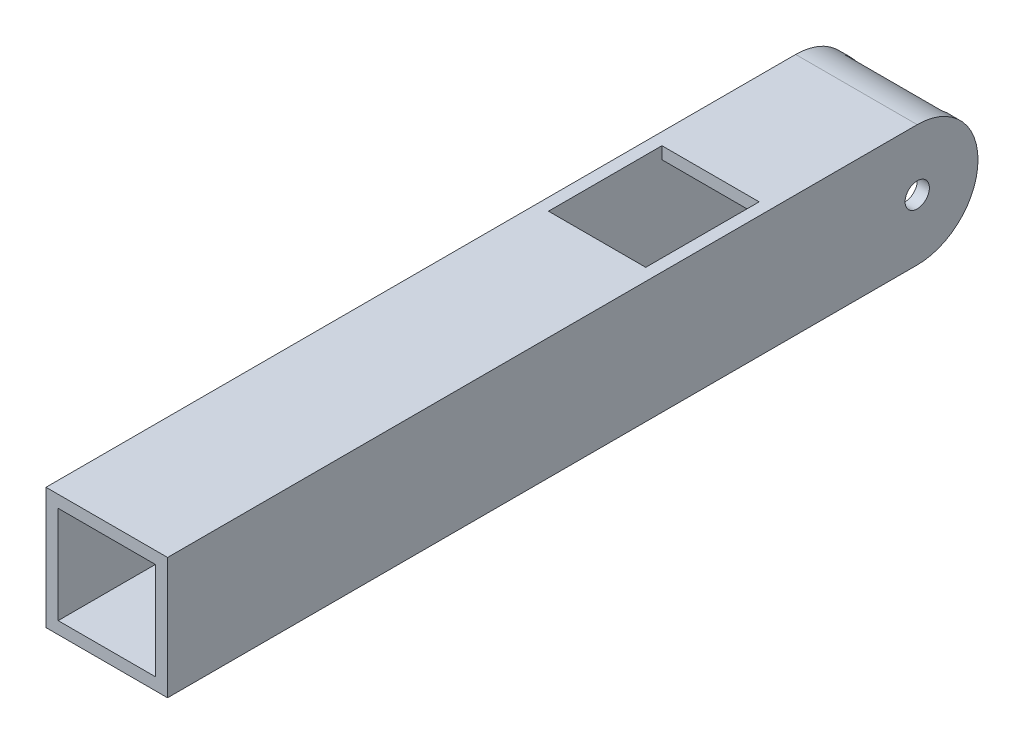
SolidWorks part; units mm, degrees
ref_plane "Plan de face" through (0, 0, 0) normal (0, 0, 1) x (1, 0, 0)
ref_plane "Plan de dessus" through (0, 0, 0) normal (0, 1, 0) x (1, 0, 0)
ref_plane "Plan de droite" through (0, 0, 0) normal (1, 0, 0) x (0, 0, -1)
sketch "Esquisse1" plane through (0, 0, 0) normal (0, 0, 1) x (1, 0, 0)
  line L1 (-7.5, -7.5) -> (7.5, -7.5)
  line L2 (-7.5, -7.5) -> (-7.5, 7.5)
  line L3 (-7.5, 7.5) -> (7.5, 7.5)
  line L4 (7.5, -7.5) -> (7.5, 7.5)
  line L5 (-7.5, -7.5) -> (7.5, 7.5) construction
  line L6 (-7.5, 7.5) -> (7.5, -7.5) construction
  point P0 (0, 0)
  dimension "D1" = 15
  dimension "D2" = 15
extrude "Extrusion1" add sketch "Esquisse1" along normal blind 100
sketch "Esquisse2" plane through (0, 0, 100) normal (0, 0, 1) x (1, 0, 0)
  line L0 (7.5, 7.5) -> (-7.5, 7.5) construction
  line L1 (-6, -6) -> (6, -6)
  line L2 (-6, -6) -> (-6, 6)
  line L3 (-6, 6) -> (6, 6)
  line L4 (6, -6) -> (6, 6)
  line L5 (-6, -6) -> (6, 6) construction
  line L6 (-6, 6) -> (6, -6) construction
  line L7 (7.5, -7.5) -> (7.5, 7.5) construction
  point P0 (0, 0)
  dimension "D1" = 1.5
  dimension "D2" = 1.5
extrude "Extrusion2" cut sketch "Esquisse2" against normal through all
fillet "Congé1" radius 7.5 2 edges at (0, -7.5, 0) (0, 7.5, 0)
sketch "Esquisse3" plane through (7.5, 0, 0) normal (1, 0, 0) x (0, 0, -1)
  circle A0 centre (-7.5, 0) radius 1.5
  arc A1 (0, 0) -> (-7.5, 7.5) centre (-7.5, 0) ccw construction
  dimension "D1" = 3
extrude "Extrusion3" cut sketch "Esquisse3" against normal through all
sketch "Esquisse4" plane through (0, 7.5, 0) normal (0, 1, 0) x (-1, 0, 0)
  line L0 (-7.5, 7.5) -> (7.5, 7.5) construction
  line L1 (-6, 39.5) -> (6, 39.5)
  line L2 (-6, 39.5) -> (-6, 25.5)
  line L3 (-6, 25.5) -> (6, 25.5)
  line L4 (6, 39.5) -> (6, 25.5)
  line L5 (-6, 39.5) -> (6, 25.5) construction
  line L6 (-6, 25.5) -> (6, 39.5) construction
  line L7 (7.5, 100) -> (7.5, 7.5) construction
  point P0 (0, 32.5)
  dimension "D1" = 14
  dimension "D2" = 12
  dimension "D3" = 25
  dimension "D4" = 7.5
extrude "Enlèv. mat.-Extru.1" cut sketch "Esquisse4" against normal blind 3
